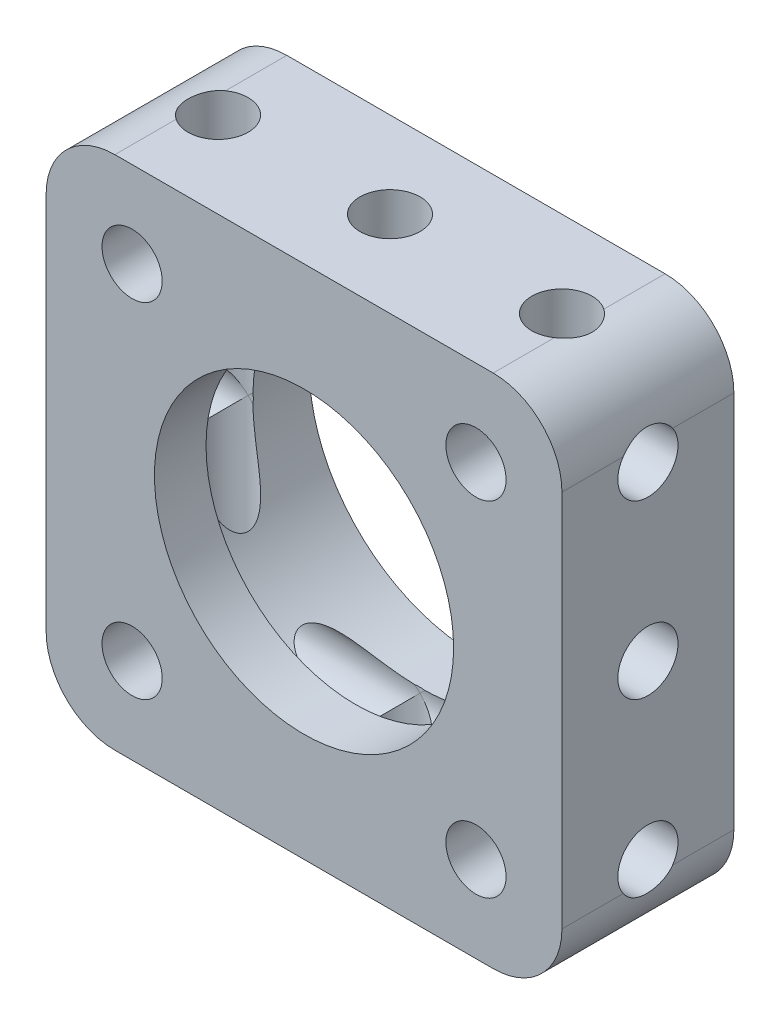
SolidWorks part; units mm, degrees
ref_plane "Plan de face" through (0, 0, 0) normal (0, 0, 1) x (1, 0, 0)
ref_plane "Plan de dessus" through (0, 0, 0) normal (0, 1, 0) x (1, 0, 0)
ref_plane "Plan de droite" through (0, 0, 0) normal (1, 0, 0) x (0, 0, -1)
sketch "Esquisse1" plane through (0, 0, 0) normal (0, 0, 1) x (1, 0, 0)
  line L0 (-15, -15) -> (-15, 15)
  line L1 (-15, 15) -> (15, 15)
  line L2 (15, 15) -> (15, -15)
  line L3 (15, -15) -> (-15, -15) construction
  line L4 (0, 26.751) -> (0, -33.9532) construction
  line L7 (-15, -15) -> (15, -15)
  line L10 (10, 10) -> (10, -10) construction
  circle A0 centre (0, 0) radius 9.7
  circle A1 centre (10, 10) radius 1.75
  circle A2 centre (-10, 10) radius 1.75
  circle A3 centre (-10, -10) radius 1.75
  circle A4 centre (10, -10) radius 1.75
  dimension "D1" = 19.4
  dimension "D10" = 3.5
  dimension "D2" = 15
  dimension "D4" = 30
  dimension "D6" = 30
  dimension "D8" = 5
  dimension "D9" = 5
  dimension "D13" = 20
  dimension "D11" = 2
  dimension "D12" = 2
extrude "Boss.-Extru.1" add sketch "Esquisse1" along normal blind 10
sketch "Esquisse2" plane through (0, 0, 10) normal (0, 0, 1) x (1, 0, 0)
  circle A0 centre (0, 0) radius 9.7
  circle A1 centre (0, 0) radius 8.7
  circle A2 centre (0, 0) radius 9.7 construction
  dimension "D1" = 1
extrude "Boss.-Extru.2" add sketch "Esquisse2" against normal offset from surface (3 mm away) 7 up to face at (-8.25, -10, 0)
sketch "Esquisse3" plane through (0, -15, 0) normal (0, -1, 0) x (1, 0, 0)
  line L0 (-30, 5) -> (15, 5) construction
  line L3 (15, 10) -> (15, 0) construction
  circle A0 centre (-30, 5) radius 1.75
  circle A1 centre (-20, 5) radius 1.75
  circle A2 centre (-10, 5) radius 1.75
  circle A3 centre (0, 5) radius 1.75
  circle A4 centre (10, 5) radius 1.75
  dimension "D2" = 3.5
  dimension "D1" = 5
  dimension "D3" = 5
extrude "Enlèv. mat.-Extru.1" cut sketch "Esquisse3" against normal through all
sketch "Esquisse4" plane through (-15, 0, 0) normal (-1, 0, 0) x (0, 0, 1)
  line L0 (5, -15) -> (5, 15) construction
  line L1 (10, -15) -> (0, -15) construction
  line L2 (10, 15) -> (0, 15) construction
  circle A0 centre (5, -10) radius 1.75
  circle A1 centre (5, 0) radius 1.75
  circle A2 centre (5, 10) radius 1.75
  dimension "D1" = 5
  dimension "D2" = 3.5
  dimension "D3" = 3
extrude "Enlèv. mat.-Extru.2" cut sketch "Esquisse4" against normal through all
fillet "Congé1" radius 4 4 edges at (15, -15, 5) (-15, -15, 5) (-15, 15, 5) (15, 15, 5)
